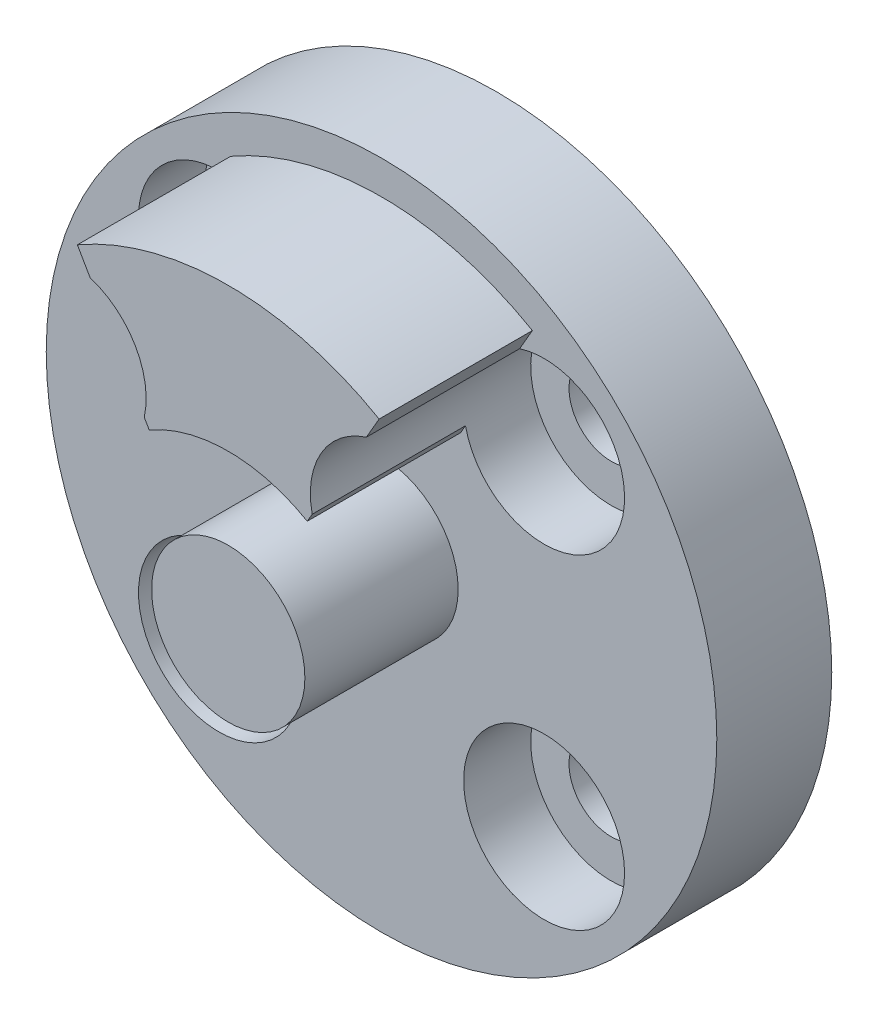
SolidWorks part; units mm, degrees
ref_plane "Front Plane" through (0, 0, 0) normal (0, 0, 1) x (1, 0, 0)
ref_plane "Top Plane" through (0, 0, 0) normal (0, 1, 0) x (1, 0, 0)
ref_plane "Right Plane" through (0, 0, 0) normal (1, 0, 0) x (0, 0, -1)
sketch "Sketch1" plane through (0, 0, 0) normal (0, 0, 1) x (1, 0, 0)
  circle A0 centre (0, 0) radius 17.5
  dimension "D1" = 35
extrude "Boss-Extrude1" add sketch "Sketch1" along normal mid plane 6
sketch "Sketch2" plane through (0, 0, 3) normal (0, 0, 1) x (1, 0, 0)
  line L3 (0, 0) -> (0, 11) construction
  line L4 (7.875, 13.6399) -> (4.125, 7.1447)
  line L5 (-4.125, 7.1447) -> (-7.875, 13.6399)
  arc A1 (4.125, 7.1447) -> (-4.125, 7.1447) centre (0, 0) ccw
  arc A6 (-7.875, 13.6399) -> (7.875, 13.6399) centre (0, 0) cw
  circle A7 centre (0, 0) radius 17.5 construction
  dimension "D2" = 7.5
  dimension "D3" = 1.75
  dimension "D1" = 30
extrude "Boss-Extrude2" add sketch "Sketch2" along normal blind 8
sketch "Sketch3" plane through (0, 0, 3) normal (0, 0, 1) x (1, 0, 0)
  circle A0 centre (0, 0) radius 4
extrude "Boss-Extrude3" add sketch "Sketch3" along normal blind 8
sketch "Sketch4" plane through (0, 0, -3) normal (0, 0, -1) x (-1, 0, 0)
  line L0 (0, 0) -> (-8.4853, 8.4853) construction
  circle A0 centre (0, 0) radius 12 construction
  circle A5 centre (-8.4853, 8.4853) radius 2.2
  circle A7 centre (8.4853, 8.4853) radius 2.2
  circle A8 centre (8.4853, -8.4853) radius 2.2
  circle A9 centre (-8.4853, -8.4853) radius 2.2
  point P14 (0, 0)
  point P17 (0, 0)
  dimension "D1" = 4
extrude "Cut-Extrude1" cut sketch "Sketch4" against normal up to surface (6 mm away) up to face at (4, 0, 3)
sketch "Sketch5" plane through (0, 0, 3) normal (0, 0, 1) x (1, 0, 0)
  circle A0 centre (-8.4853, -8.4853) radius 4.2
  circle A1 centre (-8.4853, 8.4853) radius 4.2
  circle A2 centre (8.4853, 8.4853) radius 4.2
  circle A3 centre (8.4853, -8.4853) radius 4.2
  point P12 (0, 0)
  dimension "D1" = 4
extrude "Cut-Extrude2" cut sketch "Sketch5" against normal blind 3.5 and the other way up to surface (8 mm away) other way up to face at (0, 11.1962, 11)
